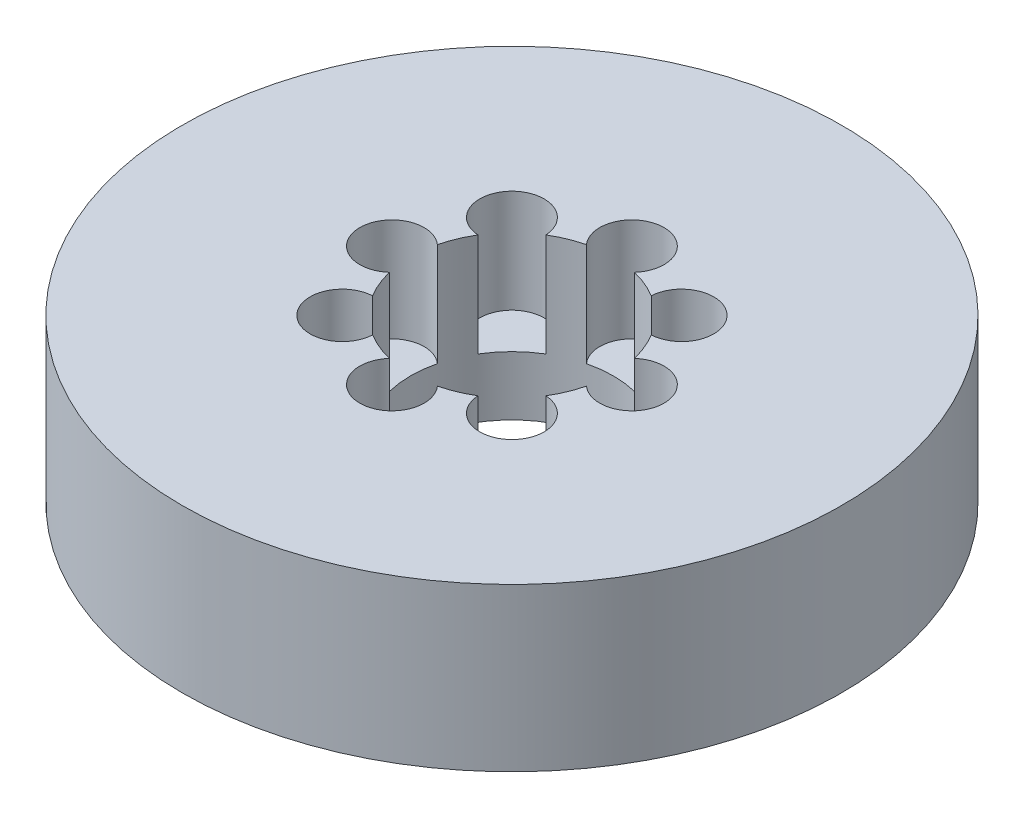
SolidWorks part; units mm, degrees
ref_plane "Front Plane" through (0, 0, 0) normal (0, 0, 1) x (1, 0, 0)
ref_plane "Top Plane" through (0, 0, 0) normal (0, 1, 0) x (1, 0, 0)
ref_plane "Right Plane" through (0, 0, 0) normal (1, 0, 0) x (0, 0, -1)
sketch "Sketch1" plane through (0, 0, 0) normal (0, 1, 0) x (1, 0, 0)
  circle A0 centre (0, 0) radius 32.5
  dimension "FLANGE_OD" = 65
extrude "Boss-Extrude1" add sketch "Sketch1" along normal blind 16
sketch "Sketch2" plane through (0, 0, 0) normal (0, 1, 0) x (1, 0, 0)
  circle A0 centre (0, 0) radius 10
  dimension "BORE_D" = 20
extrude "Cut-Extrude1" cut sketch "Sketch2" along normal through all
sketch "Sketch3" plane through (0, 16, 0) normal (0, 1, 0) x (1, 0, 0)
  circle A0 centre (0, 0) radius 11.8289 construction
  circle A1 centre (-11.8289, 0) radius 3.1722
  dimension "BOLT_D" = 6.3445
  dimension "BOLT_PCD" = 23.6579
extrude "Cut-Extrude2" cut sketch "Sketch3" against normal blind 10.1657
pattern_circular "CirPattern1" count 8 over 360 about axis through (0, 0, 0) along (0, 1, 0) of "Cut-Extrude2"
